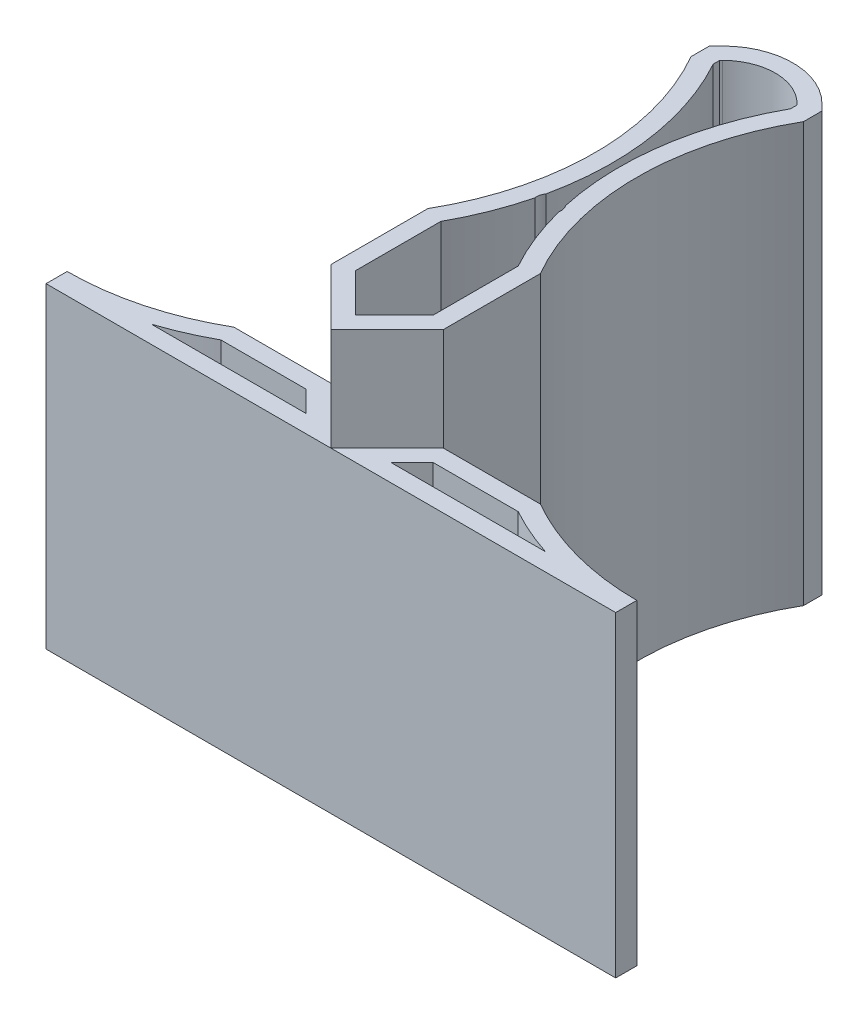
SolidWorks part; units mm, degrees
ref_plane "Front Plane" through (0, 0, 0) normal (0, 0, 1) x (1, 0, 0)
ref_plane "Top Plane" through (0, 0, 0) normal (0, 1, 0) x (1, 0, 0)
ref_plane "Right Plane" through (0, 0, 0) normal (1, 0, 0) x (0, 0, -1)
sketch "Sketch1" plane through (0, 0, 0) normal (0, 1, 0) x (1, 0, 0)
  line L0 (23.7595, 41.275) -> (41.275, 41.275) construction
  line L1 (-41.275, -41.275) -> (-23.7595, -41.275) construction
  line L2 (-41.275, -41.275) -> (-41.275, -23.7595) construction
  line L3 (-41.275, 41.275) -> (-23.7595, 41.275) construction
  line L4 (41.275, -41.275) -> (41.275, -23.7595) construction
  line L5 (-41.275, -41.275) -> (41.275, 41.275) construction
  line L6 (-41.275, 41.275) -> (41.275, -41.275) construction
  line L7 (41.275, 23.7595) -> (41.275, 41.275) construction
  line L8 (-41.275, 23.7595) -> (-41.275, 41.275) construction
  line L9 (23.7595, -41.275) -> (41.275, -41.275) construction
  line L10 (24.7569, 45.085) -> (45.085, 45.085) construction
  line L11 (45.085, 24.7569) -> (45.085, 45.085) construction
  line L12 (45.085, -45.085) -> (45.085, -24.7569) construction
  line L13 (24.7569, -45.085) -> (45.085, -45.085) construction
  line L14 (-45.085, -45.085) -> (-24.7569, -45.085) construction
  line L15 (-45.085, -45.085) -> (-45.085, -24.7569) construction
  line L16 (-45.085, 24.7569) -> (-45.085, 45.085) construction
  line L17 (-45.085, 45.085) -> (-24.7569, 45.085) construction
  line L19 (-51.435, -51.435) -> (51.435, -51.435) construction
  line L20 (-51.435, -51.435) -> (-51.435, 51.435) construction
  line L21 (-51.435, 51.435) -> (51.435, 51.435) construction
  line L22 (51.435, -51.435) -> (51.435, 51.435) construction
  line L23 (-51.435, -51.435) -> (51.435, 51.435) construction
  line L24 (-51.435, 51.435) -> (51.435, -51.435) construction
  arc A1 (-41.275, 23.7595) -> (-41.275, -23.7595) centre (0, 0) ccw construction
  arc A2 (23.7595, 41.275) -> (-23.7595, 41.275) centre (0, 0) ccw construction
  arc A3 (-23.7595, -41.275) -> (23.7595, -41.275) centre (0, 0) ccw construction
  arc A4 (41.275, -23.7595) -> (41.275, 23.7595) centre (0, 0) ccw construction
  arc A5 (45.085, -24.7569) -> (45.085, 24.7569) centre (0, 0) ccw construction
  arc A6 (-24.7569, -45.085) -> (24.7569, -45.085) centre (0, 0) ccw construction
  arc A7 (-45.085, 24.7569) -> (-45.085, -24.7569) centre (0, 0) ccw construction
  arc A8 (24.7569, 45.085) -> (-24.7569, 45.085) centre (0, 0) ccw construction
  point P0 (0, 0)
  dimension "D1" = 82.55
  dimension "D2" = 82.55
  dimension "D3" = 95.25
  dimension "D4" = 3.81
sketch "Sketch2" plane through (0, 0, 0) normal (0, 0, 1) x (1, 0, 0)
  line L0 (0, 48) -> (0, 0) construction
  line L1 (0, 0) -> (0, -9.15) construction
  line L2 (0, 48) -> (0, 66.542) construction
  dimension "Cage height" = 48
  dimension "Plate height" = 18.542
  dimension "D1" = 57.15
  dimension "D2" = 9.15
sketch "Sketch13" plane through (0, 0, 0) normal (0, 1, 0) x (1, 0, 0)
  line L0 (-51.435, -51.435) -> (51.435, -51.435) construction
  line L1 (-41.275, -41.275) -> (-23.7595, -41.275) construction
  line L2 (-41.275, -41.275) -> (-41.275, -23.7595) construction
  line L4 (-51.435, -51.435) -> (0, -51.435)
  line L5 (-41.275, -41.275) -> (-23.7595, -41.275)
  line L6 (-41.275, -41.275) -> (-41.275, -23.7595)
  line L9 (0, -47.625) -> (0, -51.435)
  line L10 (-51.435, 51.435) -> (51.435, -51.435) construction
  line L11 (-41.275, 23.7595) -> (-41.275, 41.275) construction
  line L12 (-51.435, -51.435) -> (-51.435, 51.435) construction
  line L13 (-51.435, 51.435) -> (-41.275, 41.275)
  line L14 (-41.275, 23.7595) -> (-41.275, 41.275)
  line L15 (-51.435, -51.435) -> (-51.435, 51.435)
  arc A0 (-23.7595, -41.275) -> (23.7595, -41.275) centre (0, 0) ccw construction
  arc A2 (-23.7595, -41.275) -> (0, -47.625) centre (0, 0) ccw
  arc A4 (-41.275, 23.7595) -> (-41.275, -23.7595) centre (0, 0) ccw construction
  arc A5 (-41.275, 23.7595) -> (-41.275, -23.7595) centre (0, 0) ccw
extrude "Boss-Extrude2" add sketch "Sketch13" along normal up to vertex (66.542 mm away) and the other way up to vertex (9.15 mm away) up to point (0, 66.542, 0) other way up to point (0, -9.15, 0)
sketch "Sketch15" plane through (0, 66.542, 0) normal (0, 1, 0) x (1, 0, 0)
  line L0 (0, 0) -> (-51.435, -51.435)
  line L1 (-51.435, -51.435) -> (0, -51.435)
  line L2 (0, -51.435) -> (0, 0)
  line L3 (-51.435, -51.435) -> (51.435, -51.435) construction
extrude "Cut-Extrude2" cut sketch "Sketch15" against normal up to vertex (18.542 mm away) up to point (0, 48, 0)
mirror "Mirror1" about plane through (-51.435, 66.542, 51.435) normal (1, 0, 0) of "Boss-Extrude2", "Cut-Extrude2"
sketch "Sketch16" plane through (0, -9.15, 0) normal (0, -1, 0) x (1, 0, 0)
  line L0 (-51.435, 51.435) -> (-51.435, -51.435) construction
  line L1 (-102.87, 51.435) -> (0, 51.435) construction
  line L2 (-51.435, 51.435) -> (-51.435, -51.435) construction
  circle A0 centre (-70.485, 46.355) radius 2
  circle A1 centre (-51.435, 25.4) radius 2
  circle A3 centre (-32.385, 46.355) radius 2
  circle A5 centre (-51.435, -25.4) radius 2
  dimension "D1" = 4
  dimension "D2" = 19.05
  dimension "D3" = 5.08
  dimension "D4" = 25.4
  dimension "D6" = 25.4
extrude "Cut-Extrude3" cut sketch "Sketch16" against normal blind 31.75
sketch "Sketch17" plane through (0, 66.542, 0) normal (0, 1, 0) x (1, 0, 0)
  line L0 (7.0944, 7.0944) -> (-7.0944, -7.0944)
  line L1 (7.0944, 7.0944) -> (-44.3406, 58.5294)
  line L2 (-7.0944, -7.0944) -> (-51.435, 37.2462)
  line L3 (-44.3406, 58.5294) -> (-51.435, 51.435)
  line L4 (-41.275, -41.275) -> (41.275, 41.275) construction
  line L5 (-61.595, 41.275) -> (-51.435, 51.435) construction
  line L6 (-51.435, -51.435) -> (-51.435, 51.435) construction
  line L7 (-51.435, 7.7321) -> (-51.435, 82.5591) construction
  line L8 (-95.7756, -7.0944) -> (-51.435, 37.2462)
  line L9 (-58.5294, 58.5294) -> (-51.435, 51.435)
  line L10 (-109.9644, 7.0944) -> (-58.5294, 58.5294)
  line L11 (-109.9644, 7.0944) -> (-95.7756, -7.0944)
  dimension "D1" = 20.066
extrude "Cut-Extrude4" cut sketch "Sketch17" against normal through all
fillet "Fillet2" radius 12.7 1 edges at (-51.435, 28.696, -37.2462)
sketch "Sketch18" plane through (0, 66.542, 0) normal (0, 1, 0) x (1, 0, 0)
  line L19 (-58.42, -24.5934) -> (-58.42, -39.9599)
  line L20 (-58.42, -39.9599) -> (-51.435, -46.9449)
  line L21 (-51.435, -46.9449) -> (-44.45, -39.9599)
  line L22 (-44.45, -39.9599) -> (-44.45, -24.5934)
  line L27 (-58.42, -24.5934) -> (-58.42, -39.9599)
  line L28 (-58.42, -39.9599) -> (-51.435, -46.9449)
  line L29 (-51.435, -46.9449) -> (-44.45, -39.9599)
  line L30 (-44.45, -39.9599) -> (-44.45, -24.5934)
  line L32 (-62.9101, -44.45) -> (-78.2766, -44.45)
  line L33 (-87.0077, -48.26) -> (-59.1001, -48.26)
  line L34 (-59.1001, -48.26) -> (-62.9101, -44.45)
  line L35 (-62.9101, -44.45) -> (-78.2766, -44.45)
  line L36 (-87.0077, -48.26) -> (-59.1001, -48.26)
  line L37 (-59.1001, -48.26) -> (-62.9101, -44.45)
  line L42 (-24.5934, -44.45) -> (-39.9599, -44.45)
  line L43 (-39.9599, -44.45) -> (-43.7699, -48.26)
  line L44 (-43.7699, -48.26) -> (-15.8623, -48.26)
  line L45 (-24.5934, -44.45) -> (-39.9599, -44.45)
  line L46 (-39.9599, -44.45) -> (-43.7699, -48.26)
  line L47 (-43.7699, -48.26) -> (-15.8623, -48.26)
  line L48 (-44.45, 25.7711) -> (-44.6998, 26.0209)
  line L49 (-44.45, 25.7711) -> (-44.6998, 26.0209)
  line L50 (-58.1702, 26.0209) -> (-58.42, 25.7711)
  line L51 (-58.1702, 26.0209) -> (-58.42, 25.7711)
  line L52 (-58.42, 25.7711) -> (-58.42, 24.5934)
  line L53 (-58.42, 25.7711) -> (-58.42, 24.5934)
  line L54 (-44.45, 24.5934) -> (-44.45, 25.7711)
  line L55 (-44.45, 24.5934) -> (-44.45, 25.7711)
  arc A5 (-87.0077, -48.26) -> (-78.2766, -44.45) centre (-102.87, 0) ccw
  arc A6 (-44.6998, 26.0209) -> (-58.1702, 26.0209) centre (-51.435, 19.2857) ccw
  arc A7 (-58.42, -24.5934) -> (-58.42, 24.5934) centre (-102.87, 0) ccw
  arc A8 (-44.45, 24.5934) -> (-44.45, -24.5934) centre (0, 0) ccw
  arc A9 (-44.6998, 26.0209) -> (-58.1702, 26.0209) centre (-51.435, 19.2857) ccw
  arc A10 (-58.42, -24.5934) -> (-58.42, 24.5934) centre (-102.87, 0) ccw
  arc A11 (-44.45, 24.5934) -> (-44.45, -24.5934) centre (0, 0) ccw
  arc A12 (-87.0077, -48.26) -> (-78.2766, -44.45) centre (-102.87, 0) ccw
  arc A14 (-24.5934, -44.45) -> (-15.8623, -48.26) centre (0, 0) ccw
  arc A15 (-24.5934, -44.45) -> (-15.8623, -48.26) centre (0, 0) ccw
  dimension "D1" = 3.175
  dimension "D2" = 3.175
  dimension "D3" = 3.175
extrude "Cut-Extrude5" cut sketch "Sketch18" against normal up to surface (43.942 mm away) up to face at (-51.435, 22.6, -27.4)
sketch "Sketch20" plane through (0, 22.6, 0) normal (0, 1, 0) x (1, 0, 0)
  line L0 (-58.42, -31.75) -> (-44.45, -31.75)
  line L2 (-47.0929, 19.05) -> (-55.7771, 19.05)
  line L3 (-55.7771, -19.05) -> (-47.0929, -19.05)
  line L12 (-58.42, -24.5934) -> (-58.42, -39.9599)
  line L13 (-58.42, -39.9599) -> (-51.435, -46.9449)
  line L14 (-51.435, -46.9449) -> (-44.45, -39.9599)
  line L15 (-44.45, -39.9599) -> (-44.45, -24.5934)
  line L20 (-58.42, -31.75) -> (-58.42, -39.9599)
  line L21 (-58.42, -39.9599) -> (-51.435, -46.9449)
  line L22 (-51.435, -46.9449) -> (-44.45, -39.9599)
  line L23 (-44.45, -39.9599) -> (-44.45, -31.75)
  line L25 (-44.45, 24.5934) -> (-44.45, 25.7711)
  line L26 (-44.45, 25.7711) -> (-44.6998, 26.0209)
  line L27 (-58.1702, 26.0209) -> (-58.42, 25.7711)
  line L28 (-58.42, 25.7711) -> (-58.42, 24.5934)
  circle A0 centre (-51.435, -25.4) radius 2 construction
  circle A1 centre (-51.435, 25.4) radius 2 construction
  arc A4 (-58.42, -24.5934) -> (-58.42, 24.5934) centre (-102.87, 0) ccw
  arc A5 (-44.45, 24.5934) -> (-44.45, -24.5934) centre (0, 0) ccw
  arc A7 (-55.7771, -19.05) -> (-55.7771, 19.05) centre (-102.87, 0) ccw
  arc A8 (-47.0929, 19.05) -> (-47.0929, -19.05) centre (0, 0) ccw
  arc A11 (-44.6998, 26.0209) -> (-58.1702, 26.0209) centre (-51.435, 19.2857) ccw
  dimension "D2" = 6.35
  dimension "D5" = 6.35
  dimension "D3" = 6.35
  dimension "D1" = 0
extrude "Cut-Extrude6" cut sketch "Sketch20" against normal through all
sketch "Sketch21" plane through (0, -9.15, 0) normal (0, 1, 0) x (1, 0, 0)
  circle A0 centre (-51.435, 25.4) radius 2 construction
  circle A1 centre (-51.435, -25.4) radius 2 construction
  circle A2 centre (-32.385, -46.355) radius 2 construction
  circle A3 centre (-70.485, -46.355) radius 2 construction
  circle A4 centre (-51.435, 25.4) radius 2 construction
  circle A5 centre (-51.435, -25.4) radius 2 construction
  circle A6 centre (-32.385, -46.355) radius 2 construction
  circle A7 centre (-70.485, -46.355) radius 2 construction
sketch "Sketch22" plane through (0, 0, 0) normal (0, 1, 0) x (1, 0, 0)
  line L0 (-51.435, -51.435) -> (-51.435, 51.435) construction
  line L1 (-51.435, 51.435) -> (51.435, 51.435) construction
  circle A0 centre (-51.435, -12.065) radius 2.2
  dimension "D1" = 4.4
  dimension "D2" = 63.5
extrude "Cut-Extrude7" cut sketch "Sketch22" against normal through all both and the other way through all
equation "\"tightTol\"= 0.005in"
equation "\"normTol\"= 0.01in"
equation "\"looseTol\"= 0.02in"
equation "\"Cage height@Sketch2\"=48mm"
equation "\"Plate height@Sketch2\"= 0.750000in - \"looseTol\""
equation "\"D1@Sketch16\"=4mm"
equation "\"D1@Sketch17\"=0.75in+2*\"looseTol\""
equation "\"D1@Sketch22\"=4.4mm"
